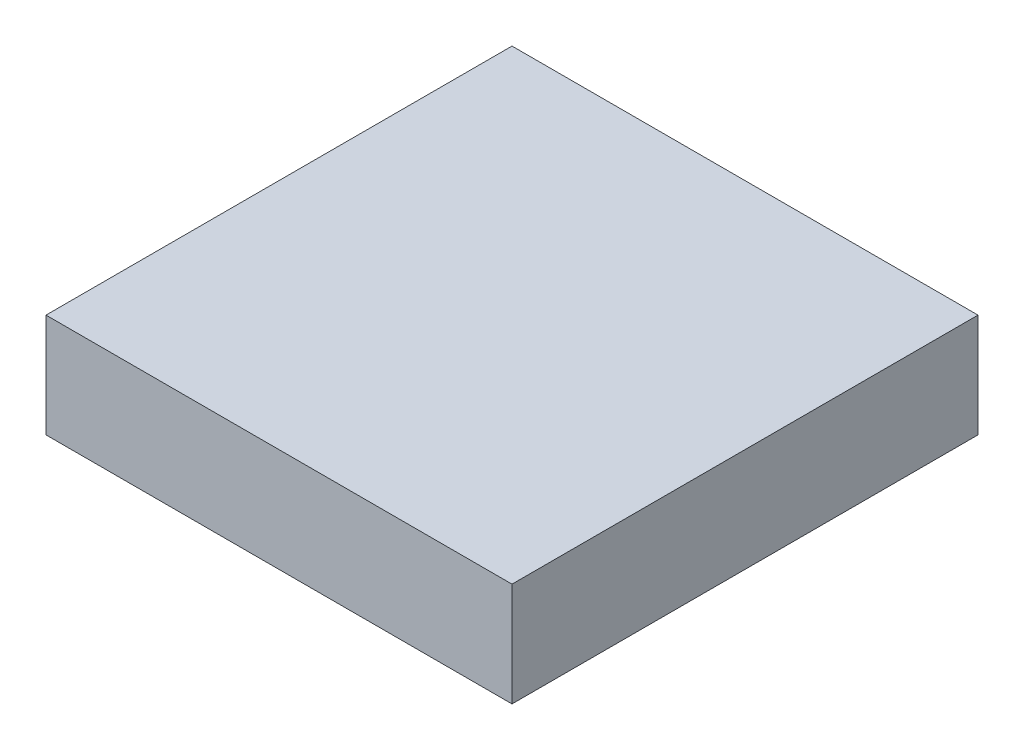
SolidWorks part; units mm, degrees
ref_plane "Front Plane" through (0, 0, 0) normal (0, 0, 1) x (1, 0, 0)
ref_plane "Top Plane" through (0, 0, 0) normal (0, 1, 0) x (1, 0, 0)
ref_plane "Right Plane" through (0, 0, 0) normal (1, 0, 0) x (0, 0, -1)
sketch "Sketch1" plane through (0, 0, 0) normal (0, 1, 0) x (1, 0, 0)
  line L1 (-49.2103, 373.03) -> (357.1897, 373.03)
  line L2 (-49.2103, 373.03) -> (-49.2103, -33.37)
  line L3 (-49.2103, -33.37) -> (357.1897, -33.37)
  line L4 (357.1897, 373.03) -> (357.1897, -33.37)
  dimension "D1" = 406.4
extrude "Boss-Extrude1" add sketch "Sketch1" along normal blind 90.4875
